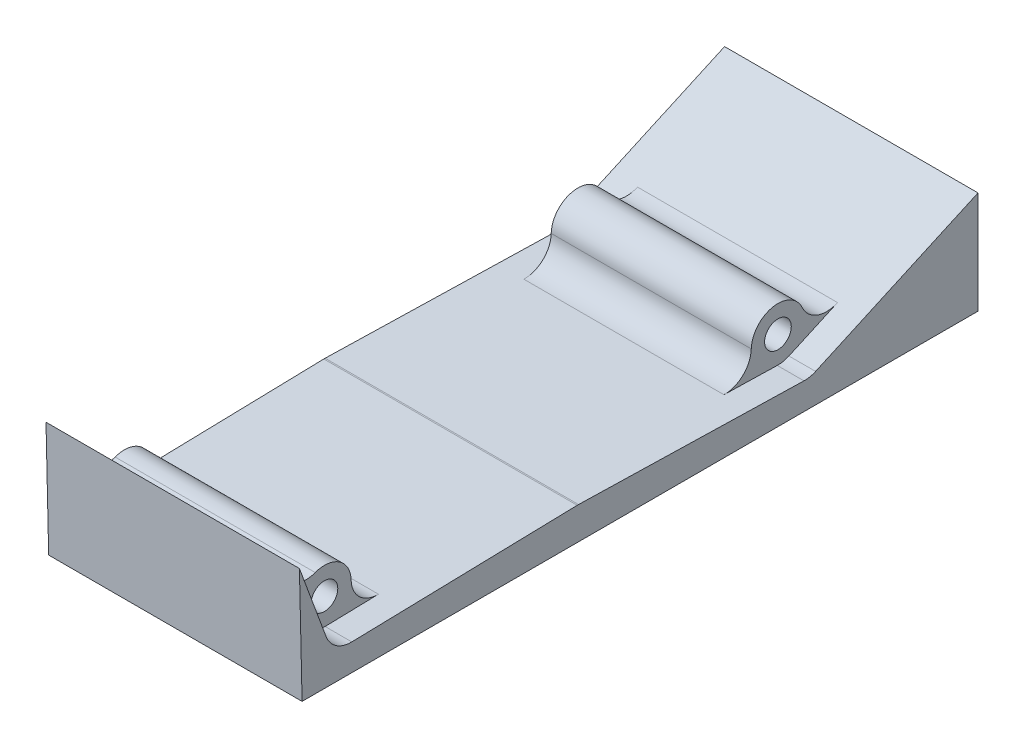
SolidWorks part; units mm, degrees
ref_plane "Front Plane" through (0, 0, 0) normal (0, 0, 1) x (1, 0, 0)
ref_plane "Top Plane" through (0, 0, 0) normal (0, 1, 0) x (1, 0, 0)
ref_plane "Right Plane" through (0, 0, 0) normal (1, 0, 0) x (0, 0, -1)
sketch "Sketch1" plane through (0, 0, 0) normal (1, 0, 0) x (0, 0, -1)
  line L0 (94.6901, -47.0615) -> (56.5901, -64.2797) construction
  line L1 (53.817, -64.8412) -> (0.158, -63.5059) construction
  line L2 (-0.158, -63.5059) -> (-53.817, -64.8412) construction
  line L3 (-59.9328, -60.6904) -> (-66.2828, -43.4722) construction
  line L4 (95.25, -46.8085) -> (56.5901, -64.2797)
  line L5 (53.817, -64.8412) -> (0.158, -63.5059)
  line L6 (-0.158, -63.5059) -> (-53.817, -64.8412)
  line L7 (-59.9328, -60.6904) -> (-66.2828, -43.4722)
  line L12 (95.25, -71.1932) -> (95.25, 0) construction
  line L13 (-66.2828, -43.4722) -> (-65.6463, -71.1932)
  line L14 (-65.6463, -71.1932) -> (95.25, -71.1932)
  line L15 (95.25, -71.1932) -> (95.25, -46.8085)
  arc A0 (53.817, -64.8412) -> (56.5901, -64.2797) centre (53.975, -58.4932) ccw construction
  arc A1 (0.158, -63.5059) -> (-0.158, -63.5059) centre (0, -69.8539) ccw construction
  arc A2 (-59.9328, -60.6904) -> (-53.817, -64.8412) centre (-53.975, -58.4932) ccw construction
  arc A3 (53.817, -64.8412) -> (56.5901, -64.2797) centre (53.975, -58.4932) ccw
  arc A4 (0.158, -63.5059) -> (-0.158, -63.5059) centre (0, -69.8539) ccw
  arc A5 (-59.9328, -60.6904) -> (-53.817, -64.8412) centre (-53.975, -58.4932) ccw
extrude "Boss-Extrude1" add sketch "Sketch1" along normal blind 60.325
ref_plane "Plane1" through (30.1625, 0, 0) normal (1, 0, 0) x (0, 0, -1)
sketch "Sketch2" plane through (30.1625, 0, 0) normal (1, 0, 0) x (0, 0, -1)
  circle A0 centre (-53.975, -58.4932) radius 6.35
  circle A1 centre (53.975, -58.4932) radius 6.35
  arc A2 (-59.9328, -60.6904) -> (-53.817, -64.8412) centre (-53.975, -58.4932) ccw construction
  arc A3 (53.817, -64.8412) -> (56.5901, -64.2797) centre (53.975, -58.4932) ccw construction
  circle A4 centre (-53.975, -58.4932) radius 3.175
  circle A5 centre (53.975, -58.4932) radius 3.175
  dimension "D1" = 6.35
extrude "Boss-Extrude2" add sketch "Sketch2" along normal mid plane 47.625
fillet "Fillet1" radius 6.35 4 edges at (30.1625, -60.6904, 59.9328) (30.1625, -64.8412, 53.817) (30.1625, -64.8412, -53.817) (30.1625, -64.2797, -56.5901)
shell "Shell1" thickness 3.175 removed face at (30.1625, -71.1932, -14.8019)
